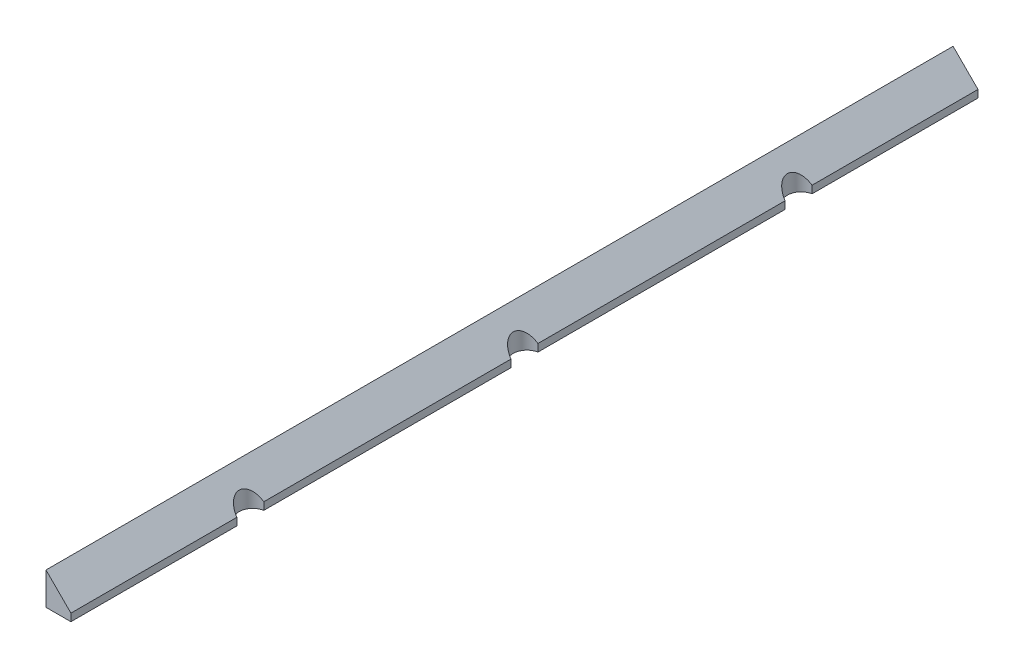
SolidWorks part; units mm, degrees
material "6061-T6 (SS)"
ref_plane "Front Plane" through (0, 0, 0) normal (0, 0, 1) x (1, 0, 0)
ref_plane "Top Plane" through (0, 0, 0) normal (0, 1, 0) x (1, 0, 0)
ref_plane "Right Plane" through (0, 0, 0) normal (1, 0, 0) x (0, 0, -1)
sketch "Sketch1" plane through (0, 0, 0) normal (0, 0, 1) x (1, 0, 0)
  line L5 (0, 0) -> (2.6, 0)
  line L6 (2.6, 0) -> (0, 2.6)
  line L7 (0, 2.6) -> (0, 0)
  line L11 (2, 0) -> (2, 0.6)
  dimension "D1" = 0.6
  dimension "D2" = 2.6
extrude "Boss-Extrude1" add sketch "Sketch1" against normal mid plane 72.8 contours L5 L11 L6 L7 region at (0.7917, 0.9042, 0)
sketch "Sketch2" plane through (0, 0, 0) normal (0, -1, 0) x (1, 0, 0)
  line L0 (2, -36.4) -> (2, 36.4) construction
  circle A12 centre (2.2, 0) radius 1.1
  circle A13 centre (2.2, 22) radius 1.1
  circle A14 centre (2.2, -22) radius 1.1
  dimension "D1" = 2.2
  dimension "D2" = 0.2
  dimension "D3" = 22
  dimension "D4" = 22
extrude "Cut-Extrude1" cut sketch "Sketch2" against normal up to surface (0.4 mm away) up to face at (1, 1.6, 0)
sketch "Sketch3" plane through (0, 0, 0) normal (0, -1, 0) x (1, 0, 0)
  line L1 (2, -20.9183) -> (2, -1.0817) construction
  circle A0 centre (2.2, 0) radius 1
  dimension "D1" = 2
  dimension "D2" = 0.2
extrude "Cut-Extrude2" [suppressed] cut sketch "Sketch3" against normal up to surface (0.4 mm away) up to face at (1.33, 1.27, 0)
